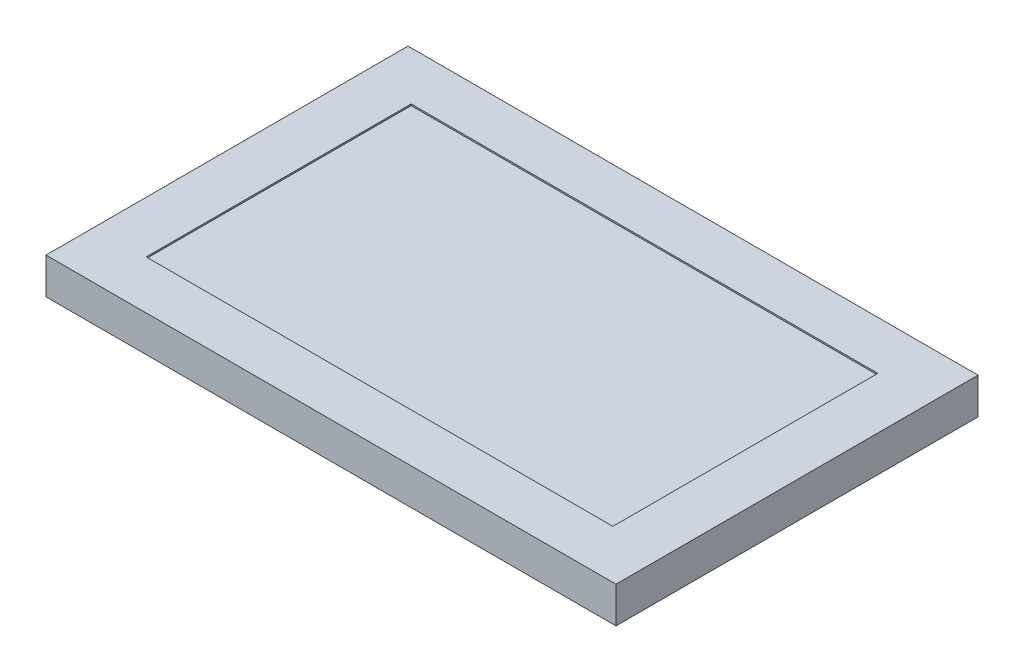
SolidWorks part; units mm, degrees
ref_plane "Front Plane" through (0, 0, 0) normal (0, 0, 1) x (1, 0, 0)
ref_plane "Top Plane" through (0, 0, 0) normal (0, 1, 0) x (1, 0, 0)
ref_plane "Right Plane" through (0, 0, 0) normal (1, 0, 0) x (0, 0, -1)
sketch "SK_Body" plane through (0, 0, 0) normal (0, 1, 0) x (1, 0, 0)
  line L1 (-94.66, 60.12) -> (94.66, 60.12)
  line L2 (-94.66, 60.12) -> (-94.66, -60.12)
  line L3 (-94.66, -60.12) -> (94.66, -60.12)
  line L4 (94.66, 60.12) -> (94.66, -60.12)
  dimension "D1" = 120.24
  dimension "D2" = 189.32
  dimension "D3" = 60.12
  dimension "D4" = 94.66
extrude "EX_Body" add sketch "SK_Body" along normal blind 12
ref_plane "PL_Zp12" through (0, 12, 0) normal (0, 1, 0) x (1, 0, 0)
sketch "SK_ActiveArea" plane through (0, 12, 0) normal (0, 1, 0) x (1, 0, 0)
  line L1 (-77.5, 44) -> (77.5, 44)
  line L2 (-77.5, 44) -> (-77.5, -44)
  line L3 (-77.5, -44) -> (77.5, -44)
  line L4 (77.5, 44) -> (77.5, -44)
  dimension "D1" = 88
  dimension "D2" = 155
  dimension "D3" = 44
  dimension "D4" = 77.5
extrude "CUT_ActiveArea" cut sketch "SK_ActiveArea" against normal blind 0.5
ref_axis "AX_X" through (0, 0, -66.132) along (0, 0, 1)
ref_axis "AX_Y" through (104.126, 0, 0) along (-1, 0, 0)
ref_axis "AX_Z" through (0, 12.6, 0) along (0, -1, 0)
